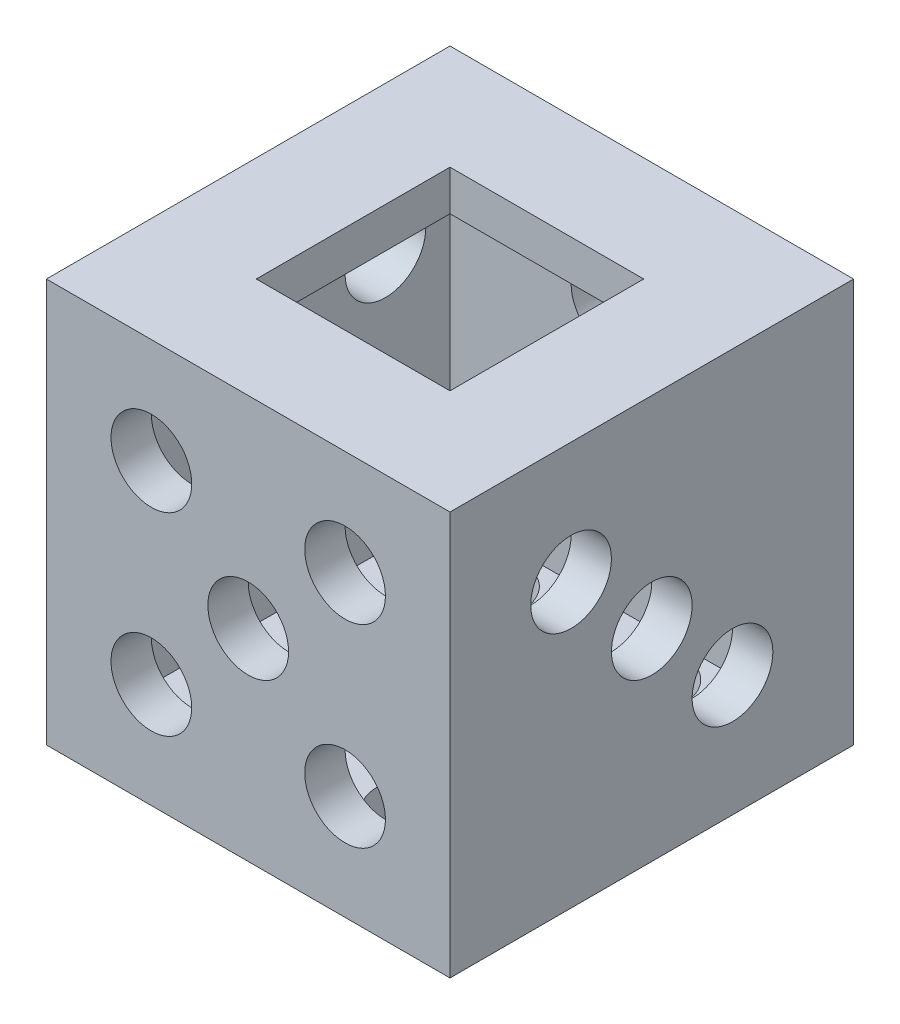
SolidWorks part; units mm, degrees
ref_plane "Front Plane" through (0, 0, 0) normal (0, 0, 1) x (1, 0, 0)
ref_plane "Top Plane" through (0, 0, 0) normal (0, 1, 0) x (1, 0, 0)
ref_plane "Right Plane" through (0, 0, 0) normal (1, 0, 0) x (0, 0, -1)
sketch "Sketch1" plane through (0, 0, 0) normal (0, 1, 0) x (1, 0, 0)
  line L1 (-12.5, 12.5) -> (12.5, 12.5)
  line L2 (-12.5, 12.5) -> (-12.5, -12.5)
  line L3 (-12.5, -12.5) -> (12.5, -12.5)
  line L4 (12.5, 12.5) -> (12.5, -12.5)
  line L5 (0, -12.5) -> (0, 12.5) construction
  line L6 (-12.5, 0) -> (12.5, 0) construction
  point P0 (0, 0)
  dimension "D1" = 25
  dimension "D2" = 25
extrude "Boss-Extrude1" add sketch "Sketch1" along normal blind 25
shell "Shell1" thickness 2.5
sketch "Sketch2" plane through (0, 25, 0) normal (0, 1, 0) x (1, 0, 0)
  line L1 (-6, 6) -> (6, 6)
  line L2 (-6, 6) -> (-6, -6)
  line L3 (-6, -6) -> (6, -6)
  line L4 (6, 6) -> (6, -6)
  line L5 (0, -6) -> (0, 6) construction
  line L6 (-6, 0) -> (6, 0) construction
  point P0 (0, 0)
  dimension "D1" = 12
  dimension "D2" = 12
extrude "Cut-Extrude1" cut sketch "Sketch2" against normal blind 15
sketch "Sketch3" plane through (0, 0, 0) normal (0, -1, 0) x (1, 0, 0)
  line L1 (10, 10) -> (-10, 10) construction
  line L2 (10, 10) -> (10, -10) construction
  line L3 (10, -10) -> (-10, -10) construction
  line L4 (-10, 10) -> (-10, -10) construction
  line L5 (0, -10) -> (0, 10) construction
  line L6 (10, 0) -> (-10, 0) construction
  line L7 (5, -7) -> (-5, -7) construction
  line L8 (5, -7) -> (5, 7) construction
  line L9 (5, 7) -> (-5, 7) construction
  line L10 (-5, -7) -> (-5, 7) construction
  line L11 (0, 7) -> (0, -7) construction
  line L12 (5, 0) -> (-5, 0) construction
  circle A0 centre (-5, 7) radius 2.5
  circle A1 centre (-5, 0) radius 2.5
  circle A2 centre (-5, -7) radius 2.5
  circle A3 centre (5, 7) radius 2.5
  circle A4 centre (5, 0) radius 2.5
  circle A5 centre (5, -7) radius 2.5
  point P0 (0, 0)
  point P4 (0, 0)
  dimension "D5" = 5
  dimension "D6" = 5
  dimension "D7" = 5
  dimension "D8" = 5
  dimension "D1" = 20
  dimension "D2" = 20
  dimension "D3" = 10
  dimension "D4" = 14
extrude "Cut-Extrude2" cut sketch "Sketch3" against normal blind 15
sketch "Sketch4" plane through (12.5, 0, 0) normal (1, 0, 0) x (0, 0, -1)
  line L4 (-12.5, 0) -> (12.5, 0)
  line L5 (12.5, 0) -> (12.5, 25)
  line L6 (12.5, 25) -> (-12.5, 25)
  line L7 (-12.5, 25) -> (-12.5, 0)
  line L8 (-12.5, 0) -> (12.5, 0)
  line L10 (12.5, 25) -> (-12.5, 25)
  line L11 (-12.5, 25) -> (-12.5, 0)
  circle A0 centre (-5, 17.5) radius 2.5
  circle A1 centre (0, 12.5) radius 2.5
  circle A2 centre (5, 7.5) radius 2.5
  dimension "D5" = 5
  dimension "D6" = 5
  dimension "D7" = 5
  dimension "D1" = 0
extrude "Cut-Extrude6" cut sketch "Sketch4" against normal blind 15 contours A0
extrude "Cut-Extrude7" cut sketch "Sketch4<3>" against normal blind 15 contours A1 | A2 region at (12.5, 12.5, 0) region at (12.5, 7.5, -5)
sketch "Sketch4<3>" plane through (12.5, 0, 0) normal (1, 0, 0) x (0, 0, -1) same geometry as "Sketch4"
sketch "Sketch5" plane through (-12.5, 0, 0) normal (-1, 0, 0) x (0, 0, 1)
  line L0 (-12.5, 12.5) -> (0, 12.5) construction
  line L2 (-10, 22.5) -> (10, 22.5) construction
  line L3 (-10, 22.5) -> (-10, 2.5) construction
  line L4 (-12.5, 0) -> (12.5, 0)
  line L5 (12.5, 0) -> (12.5, 25)
  line L6 (12.5, 25) -> (-12.5, 25)
  line L7 (-12.5, 25) -> (-12.5, 0)
  line L8 (-12.5, 0) -> (12.5, 0)
  line L9 (12.5, 0) -> (12.5, 25)
  line L10 (12.5, 25) -> (-12.5, 25)
  line L11 (-12.5, 25) -> (-12.5, 0)
  line L12 (-10, 2.5) -> (10, 2.5) construction
  line L13 (10, 22.5) -> (10, 2.5) construction
  line L14 (0, 2.5) -> (0, 22.5) construction
  line L15 (-10, 12.5) -> (10, 12.5) construction
  line L16 (-6, 18.5) -> (6, 18.5) construction
  line L17 (-6, 18.5) -> (-6, 6.5) construction
  line L18 (-6, 6.5) -> (6, 6.5) construction
  line L19 (6, 18.5) -> (6, 6.5) construction
  line L20 (0, 6.5) -> (0, 18.5) construction
  line L21 (-6, 12.5) -> (6, 12.5) construction
  circle A0 centre (-6, 18.5) radius 2.5
  circle A1 centre (6, 18.5) radius 2.5
  circle A2 centre (6, 6.5) radius 2.5
  circle A3 centre (-6, 6.5) radius 2.5
  dimension "D6" = 5
  dimension "D7" = 5
  dimension "D8" = 5
  dimension "D9" = 5
  dimension "D2" = 20
  dimension "D3" = 20
  dimension "D4" = 12
  dimension "D5" = 12
  dimension "D1" = 0
extrude "Cut-Extrude8" cut sketch "Sketch5" against normal blind 15 contours A0
extrude "Cut-Extrude9" cut sketch "Sketch5<4>" against normal blind 15 contours A1
sketch "Sketch5<4>" plane through (-12.5, 0, 0) normal (-1, 0, 0) x (0, 0, 1) same geometry as "Sketch5"
extrude "Cut-Extrude10" cut sketch "Sketch5<5>" against normal blind 15 contours A3 | A2
sketch "Sketch5<5>" plane through (-12.5, 0, 0) normal (-1, 0, 0) x (0, 0, 1) same geometry as "Sketch5"
sketch "Sketch7" plane through (0, 0, 12.5) normal (0, 0, 1) x (1, 0, 0)
  line L0 (0, 25) -> (0, 12.5) construction
  line L2 (-10, 22.5) -> (10, 22.5) construction
  line L3 (-10, 22.5) -> (-10, 2.5) construction
  line L4 (-12.5, 0) -> (12.5, 0)
  line L5 (12.5, 0) -> (12.5, 25)
  line L6 (12.5, 25) -> (-12.5, 25)
  line L7 (-12.5, 25) -> (-12.5, 0)
  line L8 (-12.5, 0) -> (12.5, 0)
  line L9 (12.5, 0) -> (12.5, 25)
  line L10 (12.5, 25) -> (-12.5, 25)
  line L11 (-12.5, 25) -> (-12.5, 0)
  line L12 (-10, 2.5) -> (10, 2.5) construction
  line L13 (10, 22.5) -> (10, 2.5) construction
  line L14 (0, 2.5) -> (0, 22.5) construction
  line L15 (-10, 12.5) -> (10, 12.5) construction
  line L16 (-6, 18.5) -> (6, 18.5) construction
  line L17 (-6, 18.5) -> (-6, 6.5) construction
  line L18 (-6, 6.5) -> (6, 6.5) construction
  line L19 (6, 18.5) -> (6, 6.5) construction
  line L20 (0, 6.5) -> (0, 18.5) construction
  line L21 (-6, 12.5) -> (6, 12.5) construction
  circle A0 centre (-6, 18.5) radius 2.5
  circle A1 centre (0, 12.5) radius 2.5
  circle A2 centre (6, 18.5) radius 2.5
  circle A3 centre (6, 6.5) radius 2.5
  circle A4 centre (-6, 6.5) radius 2.5
  dimension "D7" = 5
  dimension "D8" = 5
  dimension "D9" = 5
  dimension "D10" = 5
  dimension "D11" = 5
  dimension "D2" = 12.5
  dimension "D3" = 20
  dimension "D4" = 20
  dimension "D5" = 12
  dimension "D6" = 12
  dimension "D1" = 0
extrude "Cut-Extrude11" cut sketch "Sketch7" against normal blind 15 contours A1 | A2 | A0 | A4 | A3
sketch "Sketch8" plane through (0, 0, -12.5) normal (0, 0, -1) x (-1, 0, 0)
  line L0 (0, 0) -> (0, 12.5) construction
  line L1 (10, 22.5) -> (-10, 2.5) construction
  line L2 (-10, 22.5) -> (10, 22.5) construction
  line L3 (-10, 22.5) -> (-10, 2.5) construction
  line L4 (-12.5, 0) -> (12.5, 0)
  line L5 (12.5, 0) -> (12.5, 25)
  line L6 (12.5, 25) -> (-12.5, 25)
  line L7 (-12.5, 25) -> (-12.5, 0)
  line L8 (-12.5, 0) -> (12.5, 0)
  line L9 (12.5, 0) -> (12.5, 25)
  line L10 (12.5, 25) -> (-12.5, 25)
  line L11 (-12.5, 25) -> (-12.5, 0)
  line L12 (-10, 2.5) -> (10, 2.5) construction
  line L13 (10, 22.5) -> (10, 2.5) construction
  line L14 (0, 2.5) -> (0, 22.5) construction
  line L15 (-10, 12.5) -> (10, 12.5) construction
  line L17 (-6, 18.5) -> (6, 18.5) construction
  line L18 (-6, 18.5) -> (-6, 6.5) construction
  line L19 (-6, 6.5) -> (6, 6.5) construction
  line L20 (6, 18.5) -> (6, 6.5) construction
  line L21 (0, 6.5) -> (0, 18.5) construction
  line L22 (-6, 12.5) -> (6, 12.5) construction
  circle A2 centre (0, 18.5) radius 2.5
  circle A3 centre (0, 6.5) radius 2.5
  dimension "D7" = 5
  dimension "D8" = 5
  dimension "D2" = 12.5
  dimension "D3" = 20
  dimension "D4" = 20
  dimension "D5" = 12
  dimension "D6" = 12
  dimension "D1" = 0
extrude "Cut-Extrude12" cut sketch "Sketch8" against normal blind 10 contours A2 | A3
